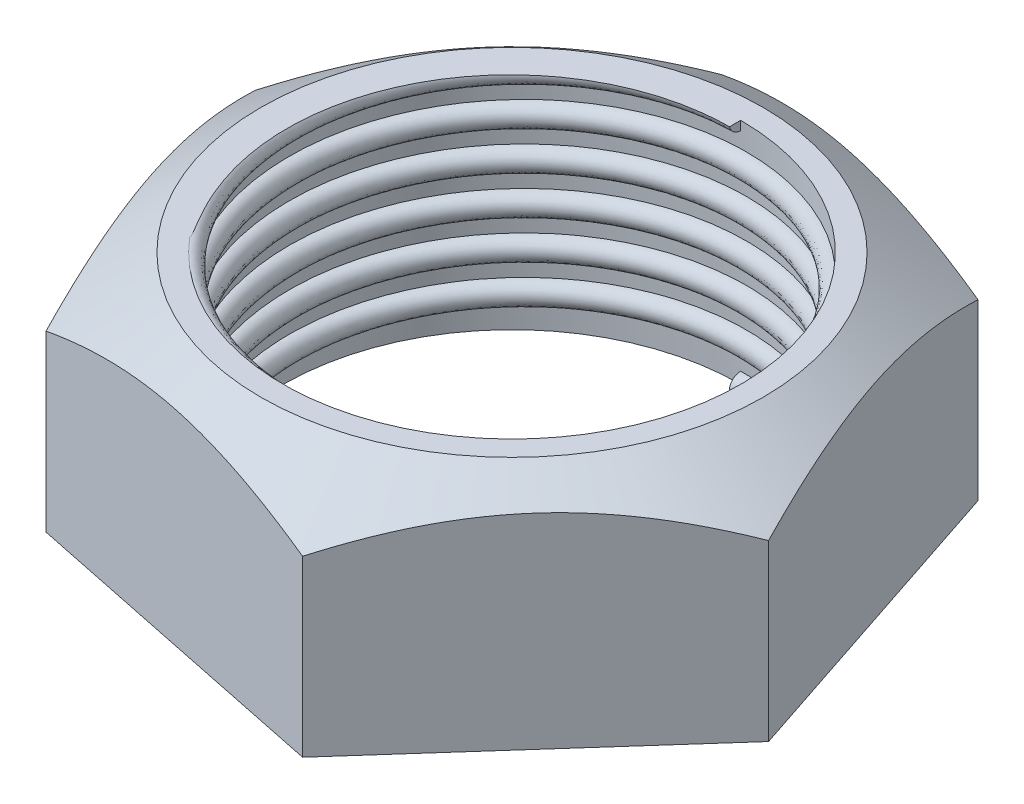
SolidWorks part; units mm, degrees
ref_plane "Front Plane" through (0, 0, 0) normal (0, 0, 1) x (1, 0, 0)
ref_plane "Top Plane" through (0, 0, 0) normal (0, 1, 0) x (1, 0, 0)
ref_plane "Right Plane" through (0, 0, 0) normal (1, 0, 0) x (0, 0, -1)
sketch "Sketch1" plane through (0, 0, 0) normal (0, 1, 0) x (1, 0, 0)
  line L1 (5.7687, -17.3995) -> (17.9528, -3.7039)
  line L2 (17.9528, -3.7039) -> (12.184, 13.6956)
  line L3 (12.184, 13.6956) -> (-5.7687, 17.3995)
  line L4 (-5.7687, 17.3995) -> (-17.9528, 3.7039)
  line L5 (-17.9528, 3.7039) -> (-12.184, -13.6956)
  line L6 (-12.184, -13.6956) -> (5.7687, -17.3995)
  circle A0 centre (0, 0) radius 15.875 construction
  circle A1 centre (0, 0) radius 12.7
  dimension "D1" = 31.75
  dimension "D3" = 25.4
  dimension "D2" = 17.9528
extrude "Boss-Extrude1" add sketch "Sketch1" along normal blind 12.7
sketch "Sketch2" plane through (0, 0, 0) normal (0, 0, 1) x (1, 0, 0)
  line L0 (13.9443, 12.7) -> (19.1676, 9.0889)
  line L1 (5.7687, 12.7) -> (17.9528, 12.7) construction
  line L3 (19.1676, 9.0889) -> (21.6287, 12.7)
  line L4 (21.6287, 12.7) -> (13.9443, 12.7)
  line L5 (0, 0) -> (0, 15.2822) construction
  dimension "D1" = 3.81
  dimension "D2" = 6.35
  dimension "D3" = 19.1676
  dimension "D4" = 4.3701
revolve "Cut-Revolve1" cut sketch "Sketch2" angle 360 about L5
sketch "Sketch3" plane through (0, 0, 0) normal (0, 1, 0) x (1, 0, 0)
  circle A0 centre (0, 0) radius 12.7
curve "Helix/Spiral1" pitch 2.14 height 12.84 radius 12.7 left hand yes centre (0, 0, 0) axis (0, 1, 0) start towards (0, 0, -1)
sketch "Sketch5" plane through (0, 0, 0) normal (1, 0, 0) x (0, 0, -1)
  circle A0 centre (12.7, 0) radius 0.635
  dimension "D1" = 1.27
sweep "Sweep1" add profiles "Sketch5" path "Helix/Spiral1"
sketch "Sketch7" plane through (0, 0, 0) normal (0, 0, 1) x (1, 0, 0)
  line L0 (-17.9528, 0) -> (-12.184, 0) construction
  line L1 (-13.9443, 12.7) -> (13.9443, 12.7)
  line L2 (-13.9443, 12.7) -> (-13.9443, 16.51)
  line L3 (-13.9443, 16.51) -> (13.9443, 16.51)
  line L4 (13.9443, 12.7) -> (13.9443, 16.51)
  line L5 (-13.9443, 0) -> (13.9443, 0)
  line L6 (-13.9443, 0) -> (-13.9443, -3.81)
  line L7 (-13.9443, -3.81) -> (13.9443, -3.81)
  line L8 (13.9443, 0) -> (13.9443, -3.81)
  dimension "D1" = 3.81
  dimension "D2" = 3.81
  dimension "D3" = 27.8887
  dimension "D4" = 13.9443
  dimension "D5" = 13.9443
extrude "Cut-Extrude2" cut sketch "Sketch7" against normal through all and the other way through all
